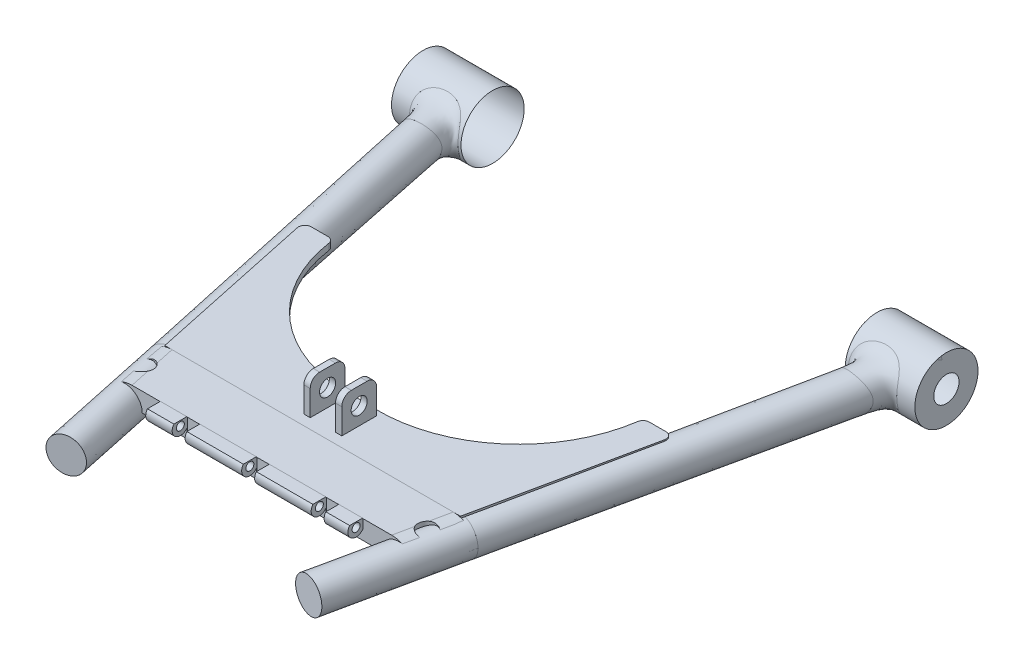
SolidWorks part; units mm, degrees
note: The reader was unsure of these and kept them because the rebuilt part matched: shared geometry of "Sketch1<4>", "Sketch1<6>".
ref_plane "Front Plane" through (0, 0, 0) normal (0, 0, 1) x (1, 0, 0)
ref_plane "Top Plane" through (0, 0, 0) normal (0, 1, 0) x (1, 0, 0)
ref_plane "Right Plane" through (0, 0, 0) normal (1, 0, 0) x (0, 0, -1)
sketch "Sketch1" plane through (0, 0, 0) normal (0, 1, 0) x (1, 0, 0)
  line L0 (0, 97.0063) -> (0, -69.8717) construction
  line L1 (-102.6594, 97.0063) -> (-77.2594, 97.0063)
  line L2 (-77.2594, 102.0863) -> (-77.2594, 97.0063) construction
  line L3 (-102.6594, 102.0863) -> (-102.6594, 109.7063) construction
  line L4 (-102.6594, 109.7063) -> (-105.1994, 109.7063)
  line L5 (-77.2594, 109.7063) -> (-77.2594, 102.0863)
  line L6 (-105.1994, 109.7063) -> (-77.2594, 109.7063)
  line L7 (-105.1994, 109.7063) -> (-105.1994, 102.0863)
  line L8 (-105.1994, 97.0063) -> (-77.2594, 97.0063)
  line L9 (-77.2594, 109.7063) -> (-77.2594, 102.0863)
  line L10 (-105.1994, 109.7063) -> (-88.4354, 102.0863) construction
  line L11 (-91.2294, 97.0063) -> (-64.8246, -27.2184)
  line L12 (-77.2594, 102.0863) -> (-105.1994, 102.0863)
  line L13 (-105.1994, 102.0863) -> (-105.1994, 109.7063)
  line L14 (-94.0234, 102.0863) -> (-77.2594, 109.7063) construction
  line L15 (-69.1362, -6.9341) -> (-59.434, -52.5791)
  line L16 (-59.434, -52.5791) -> (0, -52.5791)
  line L17 (0, 18.1627) -> (0, -32.0818)
  line L18 (-50.2445, 18.1627) -> (-74.4706, 18.1627)
  line L19 (0, 18.1627) -> (0, -32.0818)
  line L20 (-80.0806, 44.5554) -> (-76.2706, 45.3653)
  line L21 (-7.62, -34.5117) -> (-5.08, -34.5117)
  line L22 (-7.62, -34.5117) -> (-7.62, -48.4817)
  line L23 (-7.62, -48.4817) -> (-5.08, -48.4817)
  line L24 (-5.08, -34.5117) -> (-5.08, -48.4817)
  line L25 (-7.62, -34.5117) -> (-5.08, -48.4817) construction
  line L26 (-7.62, -48.4817) -> (-5.08, -34.5117) construction
  line L27 (-80.0806, 44.5554) -> (-94.0234, 41.5106)
  line L28 (-87.052, 43.033) -> (-98.8385, 97.0063)
  line L29 (-76.2706, 45.3653) -> (-87.2472, 97.0063)
  line L30 (-98.8385, 97.0063) -> (-66.4628, -52.5791)
  line L31 (-66.4628, -52.5791) -> (-59.434, -52.5791)
  line L32 (-76.2706, 45.3653) -> (-55.4519, -52.5791)
  line L33 (-66.4628, -52.5791) -> (-55.4519, -104.3319)
  arc A0 (-50.2445, 18.1627) -> (0, -32.0818) centre (0, 18.1627) ccw
  point P6 (0, 97.0063)
  point P12 (-91.2294, 103.3563)
  point P22 (-6.35, -41.4967)
  dimension "D1" = 166.878
  dimension "D2" = 7.62
  dimension "D3" = 2.54
  dimension "D4" = 27.94
  dimension "D5" = 127
  dimension "D6" = 12
  dimension "D7" = 13.97
  dimension "D8" = 2.54
  dimension "D9" = 90
  dimension "D10" = 3.81
  dimension "D11" = 90.319
  dimension "D12" = 6.35
ref_plane "Plane1" through (0, 7.62, 0) normal (0, 1, 0) x (1, 0, 0)
sketch "Sketch2" plane through (0, 7.62, 0) normal (0, 1, 0) x (1, 0, 0)
  line L0 (-73.8185, 15.0946) -> (-59.434, -52.5791)
  line L1 (-59.434, -52.5791) -> (0, -52.5791)
  line L2 (0, -52.5791) -> (0, -32.0818)
  line L3 (-71.334, 18.1627) -> (-64.5945, 18.1627)
  arc A2 (-62.0815, 15.9917) -> (0, -32.0818) centre (-6.0565, 24.2192) ccw
  arc A3 (-62.0815, 15.9917) -> (-64.5945, 18.1627) centre (-64.5945, 15.6227) ccw
  arc A4 (-71.334, 18.1627) -> (-73.8185, 15.0946) centre (-71.334, 15.6227) ccw
  point P15 (-74.4706, 18.1627)
  dimension "D1" = 2.54
extrude "Boss-Extrude1" add sketch "Sketch2" against normal blind 2.54 separate body
extrude "Boss-Extrude2" add sketch "Sketch1<4>" along normal blind 21.59 and the other way blind 0.254 contours L24 L23 L22 L21
sketch "Sketch1<4>" plane through (0, 0, 0) normal (0, 1, 0) x (1, 0, 0) same geometry as "Sketch1"
fillet "Fillet1" radius 3.81 2 edges at (-6.35, 21.59, 34.5117) (-6.35, 21.59, 48.4817)
sketch "Sketch3" plane through (-5.08, 0, 0) normal (1, 0, 0) x (0, 0, -1)
  line L0 (-41.4967, 21.59) -> (-41.4967, 7.62) construction
  line L1 (-38.3217, 21.59) -> (-44.6717, 21.59) construction
  line L2 (98.7679, 7.62) -> (-98.7679, 7.62) construction
  circle A0 centre (-41.4967, 14.605) radius 3.2397
extrude "Cut-Extrude1" cut sketch "Sketch3" against normal blind 16.764 contours A0
surface "Surface-Revolve2" sketch "Sketch1" parameters "D1"=360
surface "Surface-Revolve3" sketch "Sketch1<6>" parameters "D1"=360
sketch "Sketch1<6>" plane through (0, 0, 0) normal (0, 1, 0) x (1, 0, 0) same geometry as "Sketch1"
sketch "Sketch5" plane through (0, 0, 0) normal (0, 1, 0) x (1, 0, 0)
  ellipse E0 centre (-88.1771, 83.0948) end of major axis (-98.0873, 83.0948) minor radius 6.7446
surface "Surface-Trim8"
surface "Surface-Loft6"
mirror "Mirror2" about plane through (0, 0, 0) normal (1, 0, 0) of bodies 105 110 128 127 136 126
sketch "Sketch8" plane through (0, 7.62, 0) normal (0, 1, 0) x (1, 0, 0)
  line L0 (-59.434, -52.5791) -> (-55.09, -73.016)
  line L3 (54.9239, -73.016) -> (59.434, -52.5791)
  line L4 (59.434, -52.5791) -> (-66.4628, -52.5791)
  line L5 (-66.4628, -52.5791) -> (-62.1146, -73.016)
  line L7 (55.4519, -104.3319) -> (66.4628, -52.5791) construction
  line L8 (62.1146, -73.016) -> (66.4628, -52.5791)
  line L9 (53.0129, -49.7202) -> (66.4628, -52.5791) construction
  line L10 (66.4628, -52.5791) -> (59.434, -52.5791)
  line L11 (-0.0831, -73.016) -> (0, -52.5791) construction
  line L12 (-62.1146, -73.016) -> (62.1146, -73.016)
  circle A0 centre (-57.1853, -63.1584) radius 3.7088
  circle A1 centre (57.0974, -63.6229) radius 3.7088
extrude "Boss-Extrude5" add sketch "Sketch8" against normal up to vertex (7.62 mm away) separate body contours A0 L0 L4 L5 L12 | L12 L11 L4 L0 A0 | L11 L12 L3 A1 L4 | L3 A1 L12 L8 L10 up to point (0, 0, 32.0818)
fillet "Fillet4" radius 10 1 edges at (64.2887, 7.62, 62.7976)
fillet "Fillet5" radius 10 1 edges at (-64.2887, 7.62, 62.7976)
sketch "Sketch14" plane through (0, 7.62, 0) normal (0, 1, 0) x (1, 0, 0)
  circle A0 centre (-57.0037, -62.9026) radius 3.3951
  circle A1 centre (57.3005, -63.7253) radius 3.6939
surface "Surface-Fill2"
surface "Surface-Fill3"
surface "Surface-Knit1"
sketch "Sketch15" plane through (0, 0, 0) normal (1, 0, 0) x (0, 0, -1)
  circle A0 centre (-75.7624, 5.8441) radius 3.2978
extrude "Boss-Extrude6" add sketch "Sketch15" along normal mid plane 81.28
sketch "Sketch16" plane through (0, 7.62, 0) normal (0, 1, 0) x (1, 0, 0)
  line L0 (-40.64, -72.9836) -> (40.64, -72.9836) construction
  line L1 (-30.0011, -72.9836) -> (-24.7919, -72.9836)
  line L2 (-30.0011, -72.9836) -> (-30.0011, -92.8789)
  line L3 (-30.0011, -92.8789) -> (-24.7919, -92.8789)
  line L4 (-24.7919, -72.9836) -> (-24.7919, -92.8789)
  line L5 (-30.0011, -72.9836) -> (-24.7919, -92.8789) construction
  line L6 (-30.0011, -92.8789) -> (-24.7919, -72.9836) construction
  line L7 (-2.0611, -72.9836) -> (3.1481, -92.8789) construction
  line L8 (-2.0611, -92.8789) -> (3.1481, -72.9836) construction
  line L9 (-2.0611, -72.9836) -> (-2.0611, -92.8789)
  line L10 (-2.0611, -72.9836) -> (3.1481, -72.9836)
  line L11 (3.1481, -72.9836) -> (3.1481, -92.8789)
  line L12 (-2.0611, -92.8789) -> (3.1481, -92.8789)
  line L13 (25.8789, -72.9836) -> (31.0881, -92.8789) construction
  line L14 (25.8789, -92.8789) -> (31.0881, -72.9836) construction
  line L15 (25.8789, -72.9836) -> (25.8789, -92.8789)
  line L16 (25.8789, -72.9836) -> (31.0881, -72.9836)
  line L17 (31.0881, -72.9836) -> (31.0881, -92.8789)
  line L18 (25.8789, -92.8789) -> (31.0881, -92.8789)
  point P4 (-27.3965, -82.9313)
  point P13 (0.5435, -82.9313)
  point P18 (28.4835, -82.9313)
  dimension "D1" = 3
extrude "Cut-Extrude22" cut sketch "Sketch16" against normal mid plane 81.28 contours L9 L12 L11 L10 | L15 L18 L17 L16 | L4 L3 L2 L1
sketch "Sketch17" plane through (40.64, 0, 0) normal (1, 0, 0) x (0, 0, -1)
  line L0 (-75.7624, 2.5463) -> (-75.7624, 9.1419) construction
  arc A0 (-72.9836, 7.62) -> (-73.016, 4.0184) centre (-75.7624, 5.8441) ccw construction
  circle A1 centre (-75.7624, 5.8441) radius 1.6027
extrude "Cut-Extrude23" cut sketch "Sketch17" against normal blind 122.936
ref_plane "Plane3" through (0, 0, 69.8717) normal (0, 0, 1) x (1, 0, 0)
sketch "Sketch18" plane through (0, 0, 69.8717) normal (0, 0, 1) x (1, 0, 0)
  line L1 (-40.64, 9.1419) -> (44.45, 9.1419)
  line L2 (-40.64, 9.1419) -> (-40.64, 7.8719)
  line L3 (-40.64, 7.8719) -> (44.45, 7.8719)
  line L4 (44.45, 9.1419) -> (44.45, 7.8719)
  line L5 (-40.64, 9.1419) -> (44.45, 7.8719) construction
  line L6 (-40.64, 7.8719) -> (44.45, 9.1419) construction
  point P4 (1.905, 8.5069)
  dimension "D1" = 1.27
  dimension "D3" = 85.09
extrude "Cut-Extrude31" cut sketch "Sketch18" along normal blind 29.182
mirror "Mirror1" about plane through (0, 0, 0) normal (1, 0, 0) of bodies 137 127 128 126 110 105
